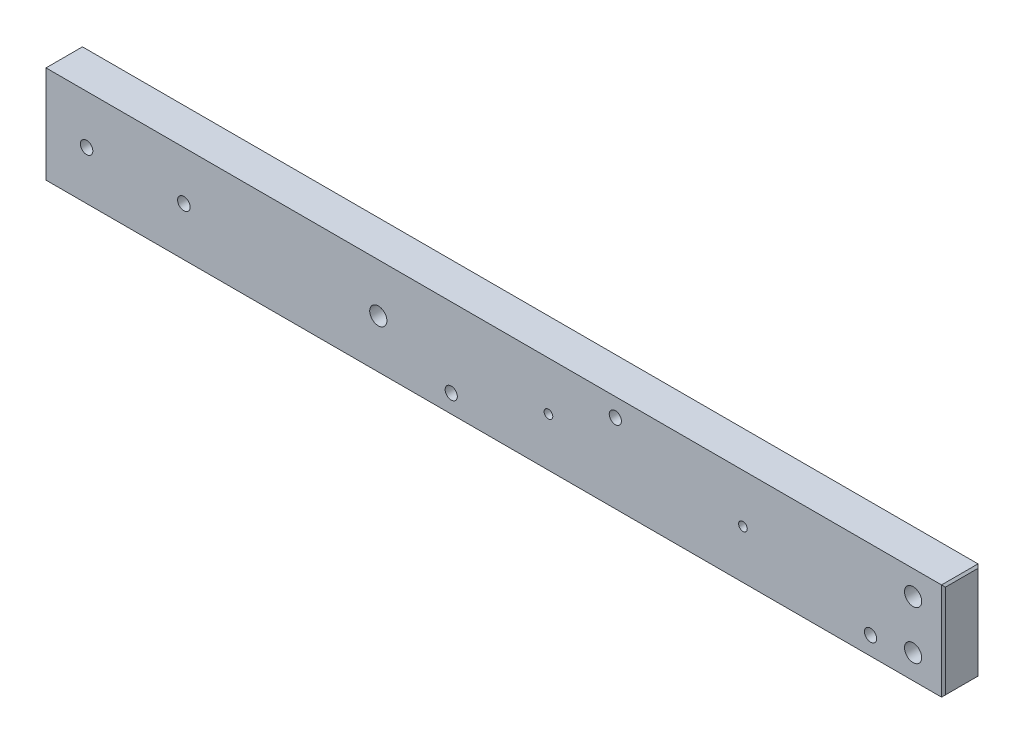
SolidWorks part; units mm, degrees
material "6061-T6 (SS)"
ref_plane "Front Plane" through (0, 0, 0) normal (0, 0, 1) x (1, 0, 0)
ref_plane "Top Plane" through (0, 0, 0) normal (0, 1, 0) x (1, 0, 0)
ref_plane "Right Plane" through (0, 0, 0) normal (1, 0, 0) x (0, 0, -1)
sketch "Sketch1" plane through (0, 0, 0) normal (0, 0, 1) x (1, 0, 0)
  line L1 (0, 0) -> (-234.95, 0)
  line L2 (0, 0) -> (0, 25.4)
  line L3 (0, 25.4) -> (-234.95, 25.4)
  line L4 (-234.95, 0) -> (-234.95, 25.4)
  dimension "D1" = 25.4
  dimension "D2" = 234.95
extrude "Boss-Extrude1" add sketch "Sketch1" along normal blind 9.525
sketch "Sketch2" plane through (0, 0, 9.525) normal (0, 0, 1) x (1, 0, 0)
  line L0 (-7.9375, 6.35) -> (-7.9375, 19.05)
  line L1 (-7.9375, 19.05) -> (-7.9375, 25.4)
  line L2 (0, 25.4) -> (-234.95, 25.4) construction
  line L3 (-7.9375, 6.35) -> (-7.9375, 0)
  line L4 (-234.95, 0) -> (0, 0) construction
  line L5 (0, 0) -> (0, 25.4) construction
  dimension "D1" = 7.9375
  dimension "D2" = 12.7
hole_wizard "#8 Clearance Hole1" positions "Sketch3" profile "Sketch4" hole size "#8" standard "ANSI Inch"
sketch "Sketch3" plane through (0, 0, 9.525) normal (0, 0, 1) x (1, 0, 0)
  point P0 (-7.9375, 6.35)
  point P3 (-7.9375, 19.05)
sketch "Sketch4" plane through (-7.9375, 6.35, 9.525) normal (1, 0, 0) x (0, -1, 0)
  line L0 (0, 0) -> (0, 26.7507)
  line L1 (0, 26.7507) -> (2.2479, 25.4)
  line L2 (2.2479, 25.4) -> (2.2479, 0)
  line L5 (2.2479, 0) -> (0, 0)
  line L10 (0, 26.7507) -> (-2.2479, 25.4) construction
  line L11 (0, -6.35) -> (0, 107.95) construction
  dimension "Hole Dia." = 4.4958
  dimension "Hole Depth" = 25.4
  dimension "Drill Angle" = 118
hole_wizard "#8 Clearance Hole2" positions "Sketch8" profile "Sketch9" hole size "#8" standard "ANSI Inch"
sketch "Sketch8" plane through (0, 0, 9.525) normal (0, 0, 1) x (1, 0, 0)
  line L0 (-211.1375, 12.7) -> (-147.6375, 12.7)
  line L1 (-211.1375, 12.7) -> (-234.95, 12.7)
  line L2 (-234.95, 25.4) -> (-234.95, 0) construction
  point P2 (-147.6375, 12.7)
  dimension "D1" = 63.5
  dimension "D2" = 23.8125
sketch "Sketch9" plane through (-147.6375, 12.7, 9.525) normal (1, 0, 0) x (0, -1, 0)
  line L0 (0, 0) -> (0, 20.4007)
  line L1 (0, 20.4007) -> (2.2479, 19.05)
  line L2 (2.2479, 19.05) -> (2.2479, 0)
  line L5 (2.2479, 0) -> (0, 0)
  line L10 (0, 20.4007) -> (-2.2479, 19.05) construction
  line L11 (0, -6.35) -> (0, 107.95) construction
  dimension "Hole Dia." = 4.4958
  dimension "Hole Depth" = 19.05
  dimension "Drill Angle" = 118
chamfer "Chamfer1" distance 0.508 angle 45 8 edges at (0, 0, 4.7625) (0, 12.7, 9.525) (0, 25.4, 4.7625) (0, 12.7, 0) (-234.95, 25.4, 4.7625) (-234.95, 12.7, 9.525) (-234.95, 0, 4.7625) (-234.95, 12.7, 0)
hole_wizard "#4-40 Tapped Hole1" positions "Sketch10" profile "Sketch12" tap size "#4-40" standard "ANSI Inch" end condition through all
sketch "Sketch10" plane through (0, 0, 0) normal (0, 0, -1) x (-1, 0, 0)
  point P0 (103.1875, 12.7)
  point P3 (52.3875, 12.7)
sketch "Sketch12" plane through (-103.1875, 12.7, 0) normal (1, 0, 0) x (0, 1, 0)
  line L0 (0, 0) -> (0, 9.525)
  line L1 (0, 9.525) -> (1.1303, 9.525)
  line L2 (1.1303, 9.525) -> (1.1303, 0)
  line L5 (1.1303, 0) -> (0, 0)
  line L11 (0, -6.35) -> (0, 107.95) construction
  dimension "Thread Major Dia." = 2.2606
  dimension "Thru Tap Drill Depth" = 9.525
hole_wizard "#4 Clearance Hole2" positions "Sketch13" profile "Sketch14" hole size "#4" standard "ANSI Inch" end condition up to next
sketch "Sketch13" plane through (0, 0, 9.525) normal (0, 0, 1) x (1, 0, 0)
  line L0 (-223.8375, 12.7) -> (-198.4375, 12.7)
  line L2 (-234.442, 25.4) -> (-234.442, 0) construction
  line L3 (-147.6375, 12.7) -> (-211.1375, 12.7) construction
  point P0 (-223.8375, 12.7)
  point P2 (-198.4375, 12.7)
  point P11 (-234.442, 12.7)
  dimension "D1" = 25.4
  dimension "D2" = 63.5
sketch "Sketch14" plane through (-223.8375, 12.7, 9.525) normal (1, 0, 0) x (0, -1, 0)
  line L0 (0, 0) -> (0, 9.525)
  line L1 (0, 9.525) -> (1.6319, 9.525)
  line L2 (1.6319, 9.525) -> (1.6319, 0)
  line L5 (1.6319, 0) -> (0, 0)
  line L11 (0, -6.35) -> (0, 107.95) construction
  dimension "Thru Hole Dia." = 3.2639
  dimension "Thru Hole Depth" = 9.525
hole_wizard "1/8 (0.125) Diameter Hole1" positions "Sketch15" profile "Sketch17" hole size "1/8" standard "ANSI Inch" end condition up to next
sketch "Sketch15" plane through (0, 0, 9.525) normal (0, 0, 1) x (1, 0, 0)
  line L1 (0, 24.892) -> (0, 0.508) construction
  line L2 (-85.725, 20.6375) -> (-19.05, 4.7625)
  line L6 (-234.442, 0) -> (-0.508, 0) construction
  line L7 (-234.442, 0) -> (-0.508, 0) construction
  line L8 (-0.508, 25.4) -> (-234.442, 25.4) construction
  line L9 (-134.9375, 0) -> (-134.9375, 25.4) construction
  point P0 (-19.05, 4.7625)
  point P2 (-85.725, 20.6375)
  point P22 (-128.5875, 4.7625)
  dimension "D1" = 85.725
  dimension "D2" = 19.05
  dimension "D3" = 4.7625
  dimension "D4" = 4.7625
  dimension "D5" = 6.35
  dimension "D6" = 4.7625
sketch "Sketch17" plane through (-19.05, 4.7625, 9.525) normal (1, 0, 0) x (0, -1, 0)
  line L0 (0, 0) -> (0, 9.525)
  line L1 (0, 9.525) -> (1.5875, 9.525)
  line L2 (1.5875, 9.525) -> (1.5875, 0)
  line L5 (1.5875, 0) -> (0, 0)
  line L11 (0, -6.35) -> (0, 107.95) construction
  dimension "Thru Hole Dia." = 3.175
  dimension "Thru Hole Depth" = 9.525
